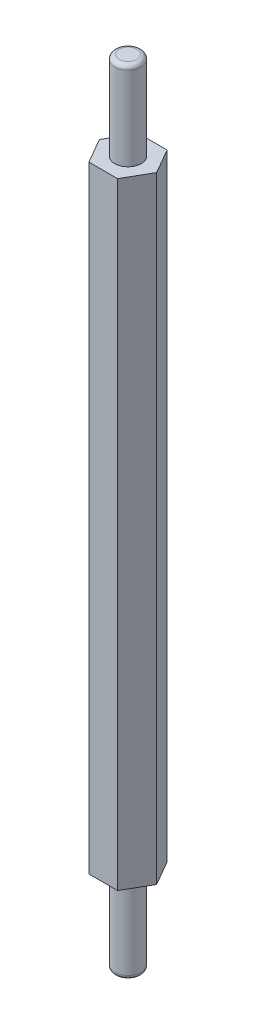
SolidWorks part; units mm, degrees
ref_plane "前视基准面" through (0, 0, 0) normal (0, 0, 1) x (1, 0, 0)
ref_plane "上视基准面" through (0, 0, 0) normal (0, 1, 0) x (1, 0, 0)
ref_plane "右视基准面" through (0, 0, 0) normal (1, 0, 0) x (0, 0, -1)
sketch "草图1" plane through (0, 0, 0) normal (0, 1, 0) x (1, 0, 0)
  circle A0 centre (0, 0) radius 1.5
  dimension "D1" = 3
extrude "凸台-拉伸1" add sketch "草图1" along normal blind 90
fillet "圆角1" radius 0.5 2 edges at (0, 0, 1.5) (0, 90, 1.5)
sketch "草图2" plane through (0, 0, 0) normal (0, 1, 0) x (1, 0, 0)
  line L1 (-1.625, 2.8146) -> (-3.25, 0)
  line L2 (-3.25, 0) -> (-1.625, -2.8146)
  line L3 (-1.625, -2.8146) -> (1.625, -2.8146)
  line L4 (1.625, -2.8146) -> (3.25, 0)
  line L5 (3.25, 0) -> (1.625, 2.8146)
  line L6 (1.625, 2.8146) -> (-1.625, 2.8146)
  circle A0 centre (0, 0) radius 3.25 construction
  circle A1 centre (0, 0) radius 1.5
  dimension "D1" = 3
  dimension "D2" = 6.5
extrude "凸台-拉伸2" add sketch "草图2" along normal blind 80
extrude "切除-拉伸2" cut sketch "草图2<3>" along normal blind 10
sketch "草图2<3>" plane through (0, 0, 0) normal (0, 1, 0) x (1, 0, 0) same geometry as "草图2"
